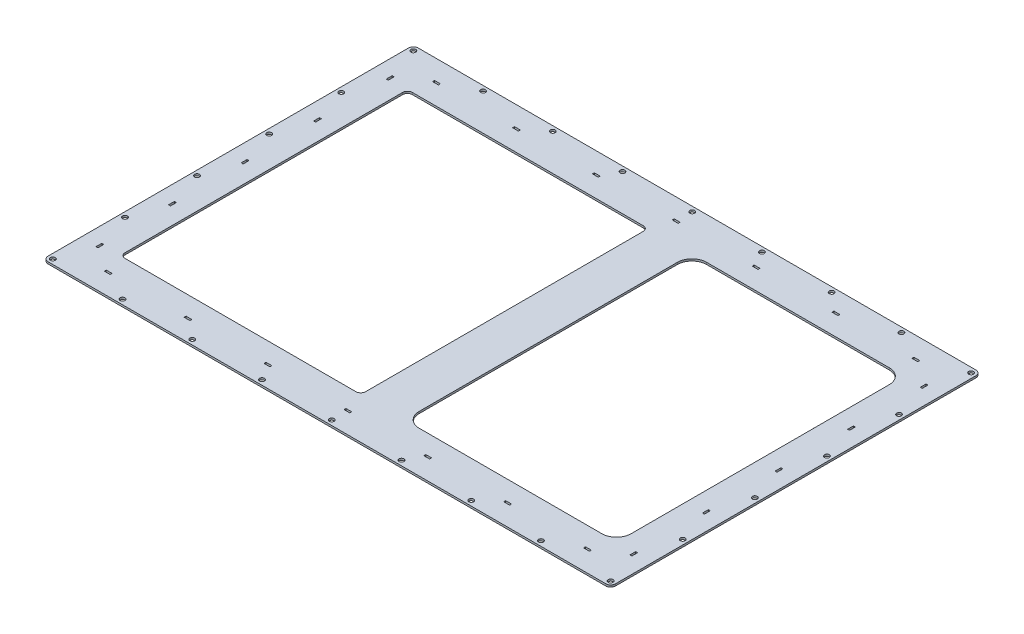
SolidWorks part; units mm, degrees
material "AISI 1020 Сталь, холоднокатаная"
ref_plane "Спереди" through (0, 0, 0) normal (0, 0, 1) x (1, 0, 0)
ref_plane "Сверху" through (0, 0, 0) normal (0, 1, 0) x (1, 0, 0)
ref_plane "Справа" through (0, 0, 0) normal (1, 0, 0) x (0, 0, -1)
sketch "Эскиз1" plane through (0, 0, 0) normal (0, 1, 0) x (1, 0, 0)
  line L1 (-582.5, -380) -> (582.5, -380)
  line L2 (-582.5, -380) -> (-582.5, 380)
  line L3 (-582.5, 380) -> (582.5, 380)
  line L4 (582.5, -380) -> (582.5, 380)
  line L5 (0, 380) -> (0, -380) construction
  line L6 (-582.5, 0) -> (582.5, 0) construction
  line L7 (-509.5, 295) -> (-15.5, 295)
  line L8 (-509.5, 295) -> (-509.5, -295)
  line L9 (-509.5, -295) -> (-15.5, -295)
  line L10 (-15.5, 295) -> (-15.5, -295)
  line L11 (74.5, 295) -> (509.5, 295)
  line L12 (74.5, 295) -> (74.5, -295)
  line L13 (74.5, -295) -> (509.5, -295)
  line L14 (509.5, 295) -> (509.5, -295)
  point P0 (0, 0)
  dimension "D1" = 1165
  dimension "D2" = 760
  dimension "D3" = 73
  dimension "D4" = 85
  dimension "D5" = 85
  dimension "D6" = 494
  dimension "D7" = 73
  dimension "D8" = 435
extrude "Бобышка-Вытянуть1" add sketch "Эскиз1" along normal mid plane 4
fillet "Скругление1" radius 10 8 edges at (582.5, 0, 380) (-582.5, 0, 380) (582.5, 0, -380) (-582.5, 0, -380) (-15.5, 0, 295) (-509.5, 0, 295) (-15.5, 0, -295) (-509.5, 0, -295)
fillet "Скругление2" radius 30 4 edges at (74.5, 0, 295) (509.5, 0, 295) (509.5, 0, -295) (74.5, 0, -295)
sketch "Эскиз2" plane through (0, 2, 0) normal (0, 1, 0) x (1, 0, 0)
  circle A0 centre (-572.5, -370) radius 5
  arc A1 (-582.5, -370) -> (-572.5, -380) centre (-572.5, -370) ccw construction
  circle A2 centre (-572.5, 370) radius 5 construction
  arc A3 (-572.5, 380) -> (-582.5, 370) centre (-572.5, 370) ccw construction
  circle A4 centre (572.5, -370) radius 5 construction
  arc A5 (572.5, -380) -> (582.5, -370) centre (572.5, -370) ccw construction
  point P11 (-572.5, 370)
  point P17 (572.5, -370)
  dimension "D1" = 10
extrude "Вырез-Вытянуть1" cut sketch "Эскиз2" against normal through all
ref_plane "Плоскость1" through (29.5, 0, 0) normal (-1, 0, 0) x (0, 0, 1)
pattern_linear "Линейный массив1" count 6 spacing 148 along (0, 0, -1) count 9 spacing 143.125 along (1, 0, 0) skipping (1, 1), (1, 2), (1, 3), (1, 4), (1, 5), (1, 6), (1, 7), (2, 1), (2, 2), (2, 3), (2, 4), (2, 5), (2, 6), (2, 7), (3, 1), (3, 2), (3, 3), (3, 4), (3, 5), (3, 6), (3, 7), (4, 1), (4, 2), (4, 3), (4, 4) of "Вырез-Вытянуть1"
sketch "Эскиз3" plane through (0, 2, 0) normal (0, 1, 0) x (1, 0, 0)
  line L4 (486, 335) -> (498, 335)
  line L5 (486, 339) -> (486, 335)
  line L6 (498, 339) -> (486, 339)
  line L7 (498, 335) -> (498, 339)
  line L8 (486, 335) -> (498, 335)
  line L9 (486, 339) -> (486, 335)
  line L10 (498, 339) -> (486, 339)
  line L11 (498, 335) -> (498, 339)
  line L12 (322, 335) -> (334, 335)
  line L13 (322, 339) -> (322, 335)
  line L14 (334, 339) -> (322, 339)
  line L15 (334, 335) -> (334, 339)
  line L16 (322, 335) -> (334, 335)
  line L17 (322, 339) -> (322, 335)
  line L18 (334, 339) -> (322, 339)
  line L19 (334, 335) -> (334, 339)
  line L20 (6, 339) -> (-6, 339)
  line L21 (6, 335) -> (6, 339)
  line L22 (-6, 335) -> (6, 335)
  line L23 (-6, 339) -> (-6, 335)
  line L24 (6, 339) -> (-6, 339)
  line L25 (6, 335) -> (6, 339)
  line L26 (-6, 335) -> (6, 335)
  line L27 (-6, 339) -> (-6, 335)
  line L28 (170, 339) -> (158, 339)
  line L29 (158, 339) -> (158, 335)
  line L30 (158, 335) -> (170, 335)
  line L31 (170, 335) -> (170, 339)
  line L32 (170, 339) -> (158, 339)
  line L33 (158, 339) -> (158, 335)
  line L34 (158, 335) -> (170, 335)
  line L35 (170, 335) -> (170, 339)
  line L36 (-498, 335) -> (-486, 335)
  line L37 (-498, 339) -> (-498, 335)
  line L38 (-486, 339) -> (-498, 339)
  line L39 (-486, 335) -> (-486, 339)
  line L40 (-498, 335) -> (-486, 335)
  line L41 (-498, 339) -> (-498, 335)
  line L42 (-486, 339) -> (-498, 339)
  line L43 (-486, 335) -> (-486, 339)
  line L44 (-170, 335) -> (-158, 335)
  line L45 (-170, 339) -> (-170, 335)
  line L46 (-158, 339) -> (-170, 339)
  line L47 (-158, 335) -> (-158, 339)
  line L48 (-170, 335) -> (-158, 335)
  line L49 (-170, 339) -> (-170, 335)
  line L50 (-158, 339) -> (-170, 339)
  line L51 (-158, 335) -> (-158, 339)
  line L52 (-334, 335) -> (-322, 335)
  line L53 (-334, 339) -> (-334, 335)
  line L54 (-322, 339) -> (-334, 339)
  line L55 (-322, 335) -> (-322, 339)
  line L56 (-334, 335) -> (-322, 335)
  line L57 (-334, 339) -> (-334, 335)
  line L58 (-322, 339) -> (-334, 339)
  line L59 (-322, 335) -> (-322, 339)
  line L60 (486, -339) -> (498, -339)
  line L61 (486, -335) -> (486, -339)
  line L62 (498, -335) -> (486, -335)
  line L63 (498, -339) -> (498, -335)
  line L64 (486, -339) -> (498, -339)
  line L65 (486, -335) -> (486, -339)
  line L66 (498, -335) -> (486, -335)
  line L67 (498, -339) -> (498, -335)
  line L68 (322, -339) -> (334, -339)
  line L69 (322, -335) -> (322, -339)
  line L70 (334, -335) -> (322, -335)
  line L71 (334, -339) -> (334, -335)
  line L72 (322, -339) -> (334, -339)
  line L73 (322, -335) -> (322, -339)
  line L74 (334, -335) -> (322, -335)
  line L75 (334, -339) -> (334, -335)
  line L76 (6, -335) -> (-6, -335)
  line L77 (6, -339) -> (6, -335)
  line L78 (-6, -339) -> (6, -339)
  line L79 (-6, -335) -> (-6, -339)
  line L80 (6, -335) -> (-6, -335)
  line L81 (6, -339) -> (6, -335)
  line L82 (-6, -339) -> (6, -339)
  line L83 (-6, -335) -> (-6, -339)
  line L84 (170, -335) -> (158, -335)
  line L85 (158, -335) -> (158, -339)
  line L86 (158, -339) -> (170, -339)
  line L87 (170, -339) -> (170, -335)
  line L88 (170, -335) -> (158, -335)
  line L89 (158, -335) -> (158, -339)
  line L90 (158, -339) -> (170, -339)
  line L91 (170, -339) -> (170, -335)
  line L92 (-498, -339) -> (-486, -339)
  line L93 (-498, -335) -> (-498, -339)
  line L94 (-486, -335) -> (-498, -335)
  line L95 (-486, -339) -> (-486, -335)
  line L96 (-498, -339) -> (-486, -339)
  line L97 (-498, -335) -> (-498, -339)
  line L98 (-486, -335) -> (-498, -335)
  line L99 (-486, -339) -> (-486, -335)
  line L100 (-170, -339) -> (-158, -339)
  line L101 (-170, -335) -> (-170, -339)
  line L102 (-158, -335) -> (-170, -335)
  line L103 (-158, -339) -> (-158, -335)
  line L104 (-170, -339) -> (-158, -339)
  line L105 (-170, -335) -> (-170, -339)
  line L106 (-158, -335) -> (-170, -335)
  line L107 (-158, -339) -> (-158, -335)
  line L108 (-334, -339) -> (-322, -339)
  line L109 (-334, -335) -> (-334, -339)
  line L110 (-322, -335) -> (-334, -335)
  line L111 (-322, -339) -> (-322, -335)
  line L112 (-334, -339) -> (-322, -339)
  line L113 (-334, -335) -> (-334, -339)
  line L114 (-322, -335) -> (-334, -335)
  line L115 (-322, -339) -> (-322, -335)
  line L116 (-546, 143) -> (-546, 155)
  line L117 (-550, 143) -> (-546, 143)
  line L118 (-550, 155) -> (-550, 143)
  line L119 (-546, 155) -> (-550, 155)
  line L120 (-546, 143) -> (-546, 155)
  line L121 (-550, 143) -> (-546, 143)
  line L122 (-550, 155) -> (-550, 143)
  line L123 (-546, 155) -> (-550, 155)
  line L124 (-550, 304) -> (-550, 292)
  line L125 (-546, 304) -> (-550, 304)
  line L126 (-546, 292) -> (-546, 304)
  line L127 (-550, 292) -> (-546, 292)
  line L128 (-550, 304) -> (-550, 292)
  line L129 (-546, 304) -> (-550, 304)
  line L130 (-546, 292) -> (-546, 304)
  line L131 (-550, 292) -> (-546, 292)
  line L132 (-550, -143) -> (-550, -155)
  line L133 (-546, -143) -> (-550, -143)
  line L134 (-546, -155) -> (-546, -143)
  line L135 (-550, -155) -> (-546, -155)
  line L136 (-550, -143) -> (-550, -155)
  line L137 (-546, -143) -> (-550, -143)
  line L138 (-546, -155) -> (-546, -143)
  line L139 (-550, -155) -> (-546, -155)
  line L140 (-550, 6) -> (-550, -6)
  line L141 (-546, 6) -> (-550, 6)
  line L142 (-546, -6) -> (-546, 6)
  line L143 (-550, -6) -> (-546, -6)
  line L144 (-550, 6) -> (-550, -6)
  line L145 (-546, 6) -> (-550, 6)
  line L146 (-546, -6) -> (-546, 6)
  line L147 (-550, -6) -> (-546, -6)
  line L148 (-550, -292) -> (-550, -304)
  line L149 (-546, -292) -> (-550, -292)
  line L150 (-546, -304) -> (-546, -292)
  line L151 (-550, -304) -> (-546, -304)
  line L152 (-550, -292) -> (-550, -304)
  line L153 (-546, -292) -> (-550, -292)
  line L154 (-546, -304) -> (-546, -292)
  line L155 (-550, -304) -> (-546, -304)
  line L176 (546, -143) -> (546, -155)
  line L177 (550, -143) -> (546, -143)
  line L178 (550, -155) -> (550, -143)
  line L179 (546, -155) -> (550, -155)
  line L180 (546, -143) -> (546, -155)
  line L181 (550, -143) -> (546, -143)
  line L182 (550, -155) -> (550, -143)
  line L183 (546, -155) -> (550, -155)
  line L184 (550, -304) -> (550, -292)
  line L185 (546, -304) -> (550, -304)
  line L186 (546, -292) -> (546, -304)
  line L187 (550, -292) -> (546, -292)
  line L188 (550, -304) -> (550, -292)
  line L189 (546, -304) -> (550, -304)
  line L190 (546, -292) -> (546, -304)
  line L191 (550, -292) -> (546, -292)
  line L192 (550, 143) -> (550, 155)
  line L193 (546, 143) -> (550, 143)
  line L194 (546, 155) -> (546, 143)
  line L195 (550, 155) -> (546, 155)
  line L196 (550, 143) -> (550, 155)
  line L197 (546, 143) -> (550, 143)
  line L198 (546, 155) -> (546, 143)
  line L199 (550, 155) -> (546, 155)
  line L200 (550, -6) -> (550, 6)
  line L201 (546, -6) -> (550, -6)
  line L202 (546, 6) -> (546, -6)
  line L203 (550, 6) -> (546, 6)
  line L204 (550, -6) -> (550, 6)
  line L205 (546, -6) -> (550, -6)
  line L206 (546, 6) -> (546, -6)
  line L207 (550, 6) -> (546, 6)
  line L208 (550, 292) -> (550, 304)
  line L209 (546, 292) -> (550, 292)
  line L210 (546, 304) -> (546, 292)
  line L211 (550, 304) -> (546, 304)
  line L212 (550, 292) -> (550, 304)
  line L213 (546, 292) -> (550, 292)
  line L214 (546, 304) -> (546, 292)
  line L215 (550, 304) -> (546, 304)
  dimension "D1" = 0
  dimension "D2" = 0
  dimension "D3" = 0
  dimension "D4" = 0
  dimension "D5" = 0
  dimension "D6" = 0
  dimension "D7" = 0
  dimension "D8" = 0
  dimension "D9" = 0
  dimension "D10" = 0
  dimension "D11" = 0
  dimension "D12" = 0
  dimension "D13" = 0
  dimension "D14" = 0
  dimension "D15" = 0
  dimension "D16" = 0
  dimension "D17" = 0
  dimension "D18" = 0
  dimension "D19" = 0
  dimension "D20" = 0
  dimension "D21" = 0
  dimension "D22" = 0
  dimension "D23" = 0
  dimension "D24" = 0
extrude "Вырез-Вытянуть2" cut sketch "Эскиз3" against normal through all
ref_plane "Плоскость2" through (-262.5, 0, 0) normal (1, 0, 0) x (0, 0, -1)
